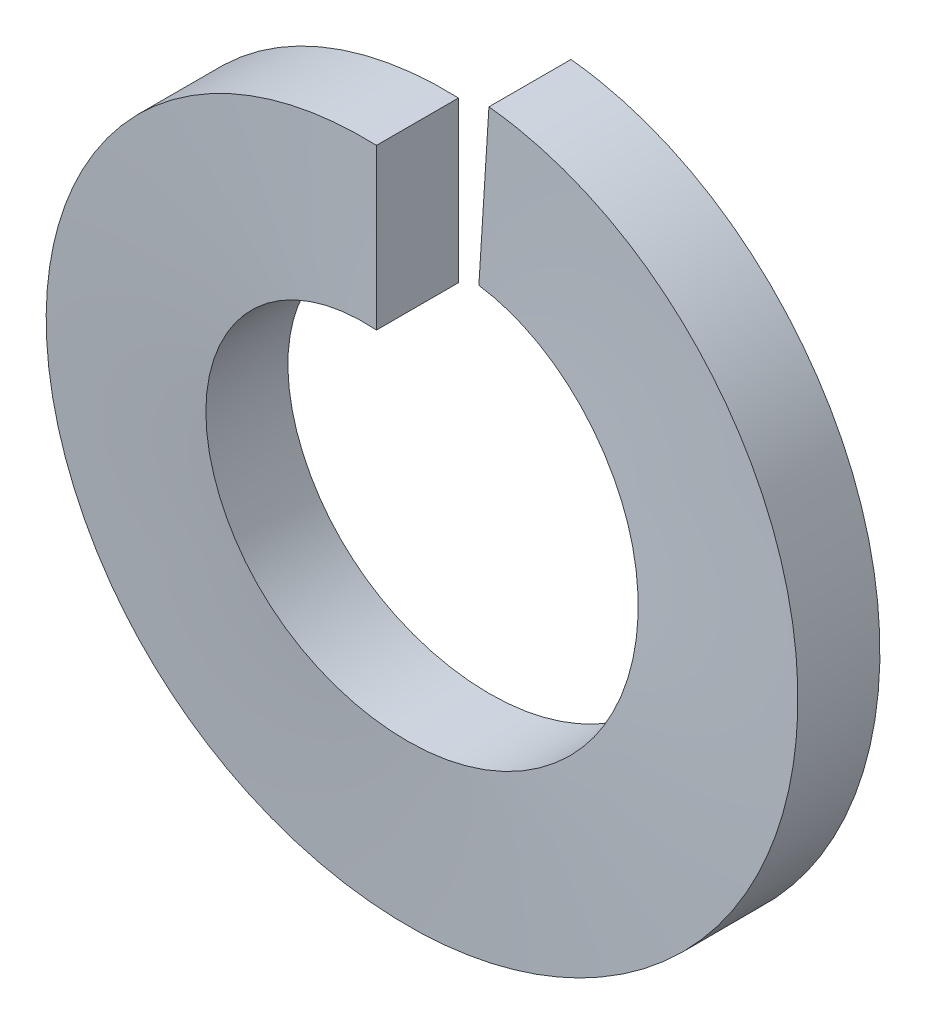
SolidWorks part; units mm, degrees
ref_plane "Front Plane" through (0, 0, 0) normal (0, 0, 1) x (1, 0, 0)
ref_plane "Top Plane" through (0, 0, 0) normal (0, 1, 0) x (1, 0, 0)
ref_plane "Right Plane" through (0, 0, 0) normal (1, 0, 0) x (0, 0, -1)
sketch "Sketch1" plane through (0, 0, 0) normal (0, 0, 1) x (1, 0, 0)
  line L0 (0, 2.1844) -> (0, 1.1938) construction
  circle A0 centre (0, 0) radius 2.1844
  circle A1 centre (0, 0) radius 1.1938 construction
  dimension "ID" = 2.3876
  dimension "OD" = 4.3688
curve "Helix/Spiral1" pitch 0.5644 height 0.5588 radius 2.1844 left hand yes centre (0, 0, 0) axis (0, 0, -1) start towards (0, 1, 0) parameters "HT"=0.5588
sketch "Sketch2" plane through (0, 0, 0) normal (1, 0, 0) x (0, 0, -1)
  line L1 (0, 2.1844) -> (-0.508, 2.1844)
  line L2 (0, 2.1844) -> (0, 1.1938)
  line L3 (0, 1.1938) -> (-0.508, 1.1938)
  line L4 (-0.508, 2.1844) -> (-0.508, 1.1938)
  dimension "THK" = 0.508
sweep "Sweep1" add profiles "Sketch2" path "Helix/Spiral1"
equation "\"HT@Helix/Spiral1\" = \"THK@Sketch2\"*1.1"
